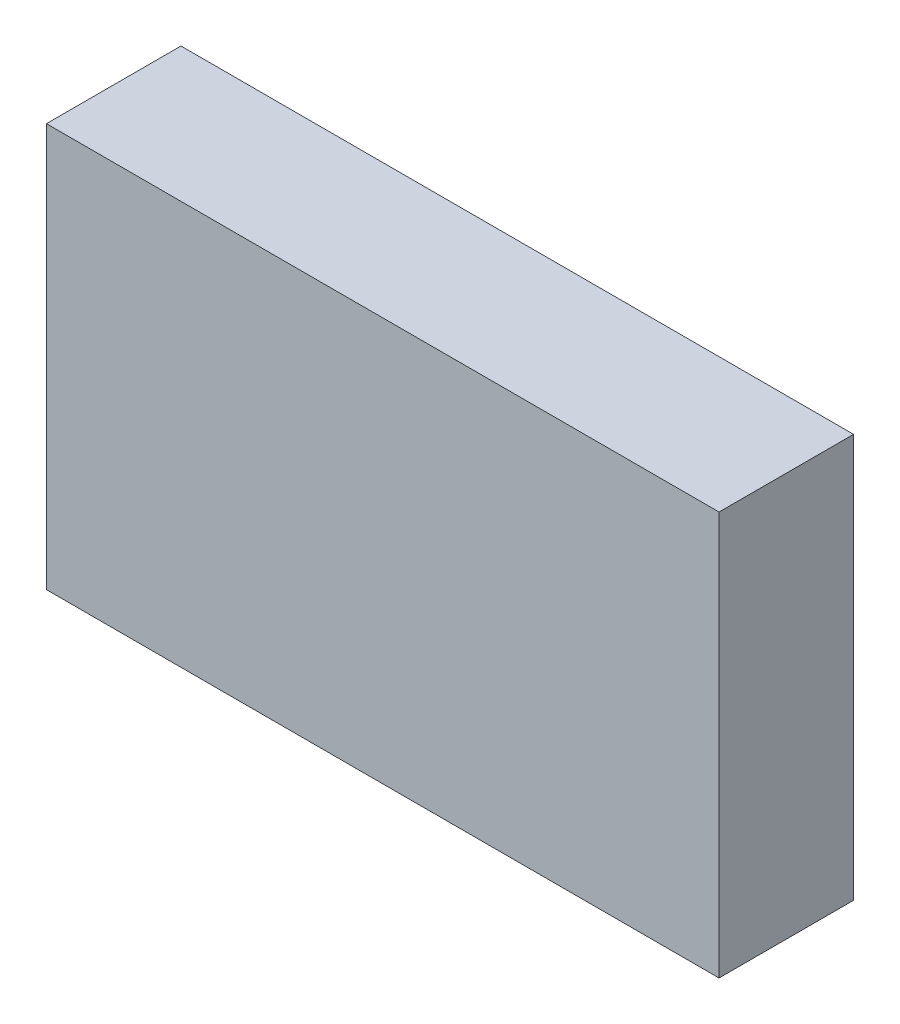
SolidWorks part; units mm, degrees
ref_plane "Front Plane" through (0, 0, 0) normal (0, 0, 1) x (1, 0, 0)
ref_plane "Top Plane" through (0, 0, 0) normal (0, 1, 0) x (1, 0, 0)
ref_plane "Right Plane" through (0, 0, 0) normal (1, 0, 0) x (0, 0, -1)
sketch "Sketch1" plane through (0, 0, 0) normal (0, 0, 1) x (1, 0, 0)
  line L1 (0, 0) -> (10, 0)
  line L2 (0, 0) -> (0, 6)
  line L3 (0, 6) -> (10, 6)
  line L4 (10, 0) -> (10, 6)
  dimension "D1" = 10
  dimension "D2" = 6
extrude "Boss-Extrude1" add sketch "Sketch1" along normal blind 2
sketch "Sketch2" plane through (0, 0, 0) normal (0, 0, -1) x (-1, 0, 0)
  line L0 (0, 0) -> (-10, 0) construction
  line L1 (-10, 0) -> (-10, 6) construction
  circle A0 centre (-5, 3) radius 2.5
  dimension "D1" = 5
  dimension "D2" = 3
  dimension "D3" = 5
extrude "Cut-Extrude1" cut sketch "Sketch2" against normal blind 1
